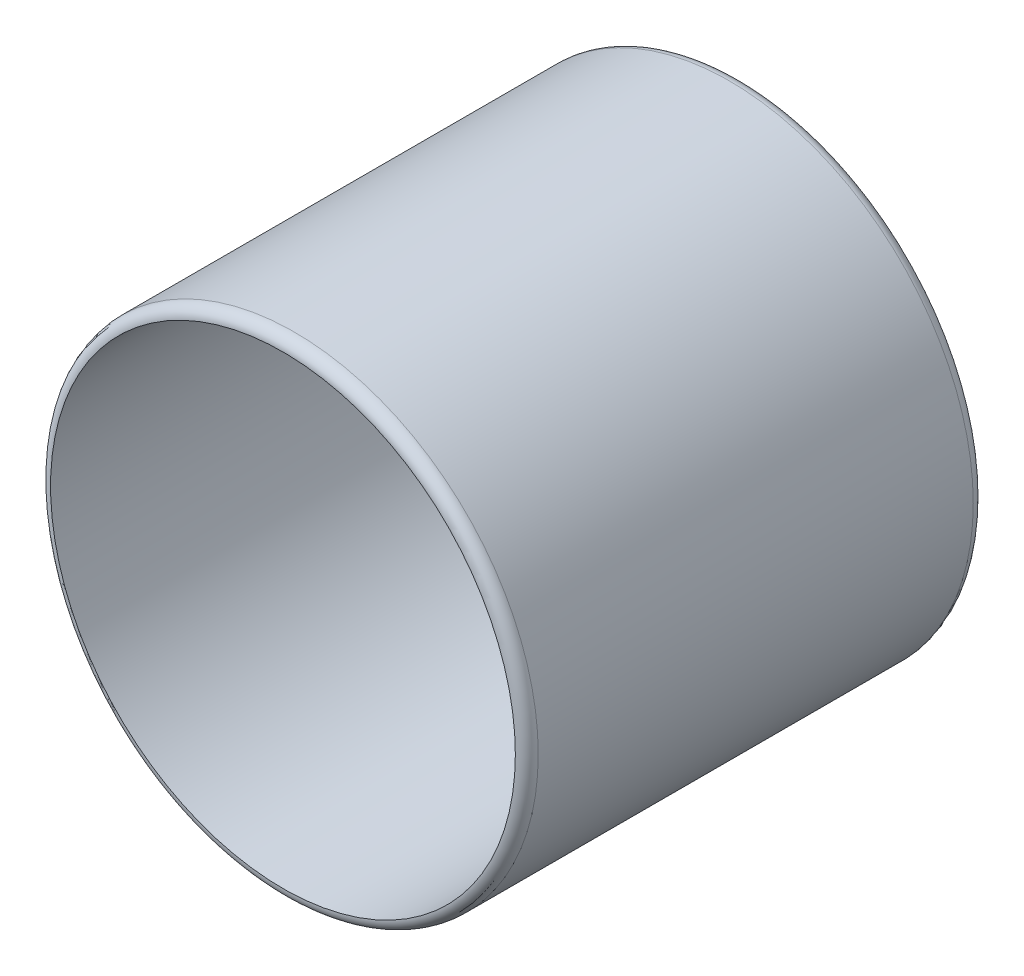
SolidWorks part; units mm, degrees
ref_plane "Front" through (0, 0, 0) normal (0, 0, 1) x (1, 0, 0)
ref_plane "Top" through (0, 0, 0) normal (0, 1, 0) x (1, 0, 0)
ref_plane "Right" through (0, 0, 0) normal (1, 0, 0) x (0, 0, -1)
sketch "Sketch1" plane through (0, 0, 0) normal (0, 0, 1) x (1, 0, 0)
  circle A0 centre (0, 0) radius 203
  dimension "D1" = 406
extrude "Extrude-Thin1" add sketch "Sketch1" along normal blind 400 thin thin type one direction wall 10
fillet "Fillet1" radius 10 2 edges at (213, 0, 0) (213, 0, 400)
